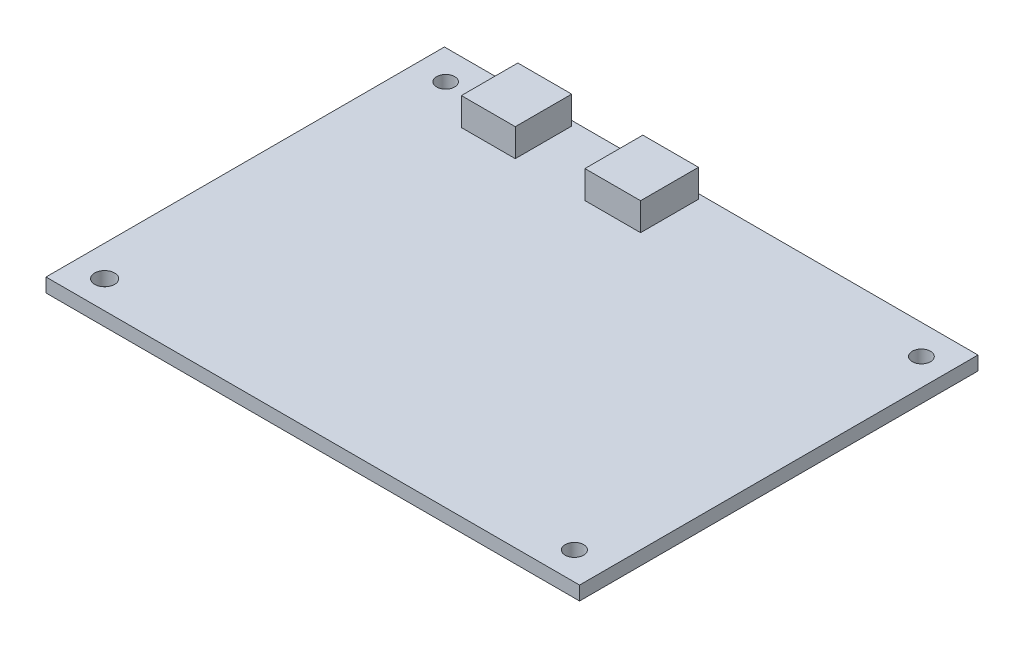
SolidWorks part; units mm, degrees
ref_plane "Plano frontal" through (0, 0, 0) normal (0, 0, 1) x (1, 0, 0)
ref_plane "Plano superior" through (0, 0, 0) normal (0, 1, 0) x (1, 0, 0)
ref_plane "Plano direito" through (0, 0, 0) normal (1, 0, 0) x (0, 0, -1)
sketch "Esboço1" plane through (0, 0, 0) normal (0, 1, 0) x (1, 0, 0)
  line L1 (-38.5, -28.75) -> (38.5, -28.75)
  line L2 (-38.5, -28.75) -> (-38.5, 28.75)
  line L3 (-38.5, 28.75) -> (38.5, 28.75)
  line L4 (38.5, -28.75) -> (38.5, 28.75)
  line L5 (-38.5, -28.75) -> (38.5, 28.75) construction
  line L6 (-38.5, 28.75) -> (38.5, -28.75) construction
  point P0 (0, 0)
  dimension "D1" = 77
  dimension "D2" = 57.5
extrude "Ressalto-extrusão1" add sketch "Esboço1" along normal blind 2
sketch "Esboço2" plane through (0, 2, 0) normal (0, 1, 0) x (1, 0, 0)
  line L1 (-27.2017, 28.0419) -> (-19.4261, 28.0419)
  line L2 (-27.2017, 28.0419) -> (-27.2017, 19.8983)
  line L3 (-27.2017, 19.8983) -> (-19.4261, 19.8983)
  line L4 (-19.4261, 28.0419) -> (-19.4261, 19.8983)
  line L5 (-9.1659, 28.0453) -> (-1.134, 28.0453)
  line L6 (-9.1659, 28.0453) -> (-9.1659, 19.6884)
  line L7 (-9.1659, 19.6884) -> (-1.134, 19.6884)
  line L8 (-1.134, 28.0453) -> (-1.134, 19.6884)
  point P8 (-29.3268, 26.7449)
  point P9 (-21.5085, 18.8573)
  point P10 (-16.5002, 26.7449)
  point P11 (-9.3472, 18.995)
  point P12 (-9.1659, 19.6884)
extrude "Ressalto-extrusão2" add sketch "Esboço2" along normal blind 4
shell "Casca1" thickness 1 removed face at (-5.1499, 4, -28.0453) removed face at (-23.3139, 4, -28.0419)
sketch "Esboço3" plane through (0, 2, 0) normal (0, 1, 0) x (1, 0, 0)
  circle A0 centre (33.7332, -24.7293) radius 1.3313
  circle A1 centre (34.5985, 24.4852) radius 1.316
  circle A2 centre (-34.0582, -24.7293) radius 1.4365
  circle A3 centre (-34.0582, 24.4852) radius 1.3029
  point P8 (-34.0582, -24.7293)
  point P9 (33.7332, -24.7293)
  point P10 (34.5985, 24.4852)
  point P11 (-34.0582, 24.4852)
extrude "Corte-extrusão1" cut sketch "Esboço3" against normal through all
